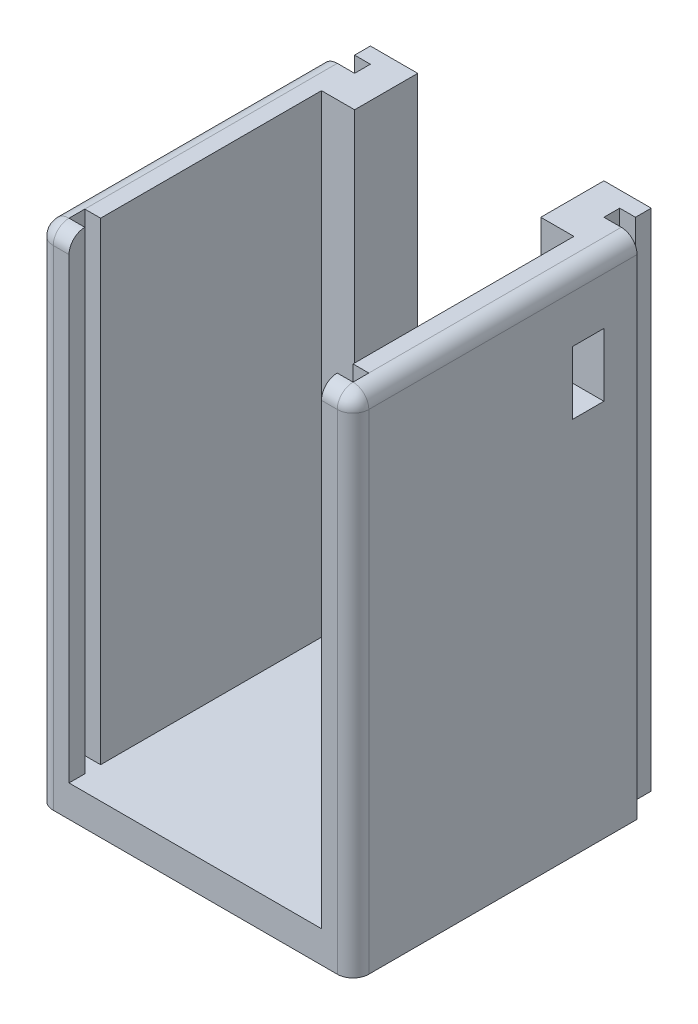
SolidWorks part; units mm, degrees
ref_plane "Front Plane" through (0, 0, 0) normal (0, 0, 1) x (1, 0, 0)
ref_plane "Top Plane" through (0, 0, 0) normal (0, 1, 0) x (1, 0, 0)
ref_plane "Right Plane" through (0, 0, 0) normal (1, 0, 0) x (0, 0, -1)
sketch "Sketch1" plane through (0, 0, 0) normal (0, 1, 0) x (1, 0, 0)
  line L0 (0, 0) -> (0, 17.9398) construction
  line L1 (50, 0) -> (-50, 0)
  line L2 (-50, 0) -> (-50, 90)
  line L3 (-50, 90) -> (-39.5, 90)
  line L4 (-39.5, 90) -> (-39.5, 95)
  line L5 (-39.5, 95) -> (-44.5, 95)
  line L6 (-44.5, 95) -> (-44.5, 100)
  line L7 (-44.5, 100) -> (44.5, 100)
  line L8 (50, 0) -> (50, 90)
  line L9 (50, 90) -> (39.5, 90)
  line L10 (39.5, 90) -> (39.5, 95)
  line L11 (39.5, 95) -> (44.5, 95)
  line L12 (44.5, 95) -> (44.5, 100)
  point P14 (0, 0)
  point P19 (0, 100)
  dimension "D1" = 50
  dimension "D2" = 10.5
  dimension "D3" = 100
  dimension "D4" = 5
  dimension "D5" = 5
  dimension "D6" = 5
extrude "Boss-Extrude1" add sketch "Sketch1" along normal blind 160
shell "Shell1" thickness 10 removed face at (0, 80, -100) removed face at (0, 160, -78.3333) removed face at (0, 80, 0)
sketch "Sketch2" plane through (0, 160, 0) normal (0, 1, 0) x (1, 0, 0)
  line L0 (-40, 5) -> (-45, 5)
  line L1 (-40, 80) -> (-40, 0) construction
  line L2 (-45, 5) -> (-45, 10)
  line L3 (-45, 10) -> (-40, 10)
  line L4 (-40, 80) -> (-40, 0) construction
  line L5 (-40, 10) -> (-40, 5)
  line L6 (-40, 0) -> (40, 0) construction
  line L7 (0, 0) -> (0, 15.7177) construction
  line L8 (40, 5) -> (45, 5)
  line L9 (40, 10) -> (40, 5)
  line L10 (45, 5) -> (45, 10)
  line L11 (45, 10) -> (40, 10)
  dimension "D1" = 5
  dimension "D2" = 5
extrude "Cut-Extrude1" cut sketch "Sketch2" against normal up to surface (150 mm away) up to face at (0, 10, -65)
fillet "Fillet1" radius 5 6 edges at (45, 160, 0) (-45, 160, 0) (50, 160, -45) (-50, 160, -45) (50, 80, 0) (-50, 80, 0)
sketch "Sketch4" plane through (50, 0, 0) normal (1, 0, 0) x (0, 0, -1)
  line L0 (79.5, 140) -> (79.5, 120)
  line L2 (79.5, 120) -> (69.5, 120)
  line L3 (69.5, 120) -> (69.5, 140)
  line L4 (69.5, 140) -> (79.5, 140)
  line L5 (90, 155) -> (90, 0) construction
  line L6 (90, 155) -> (5, 155) construction
  dimension "D1" = 10.5
  dimension "D2" = 15
  dimension "D3" = 20
  dimension "D4" = 10
extrude "Cut-Extrude2" cut sketch "Sketch4" against normal up to surface (10 mm away) up to face at (40, 85, -45)
equation "\"W\"=100"
equation "\"D3@Sketch1\"=\"W\""
